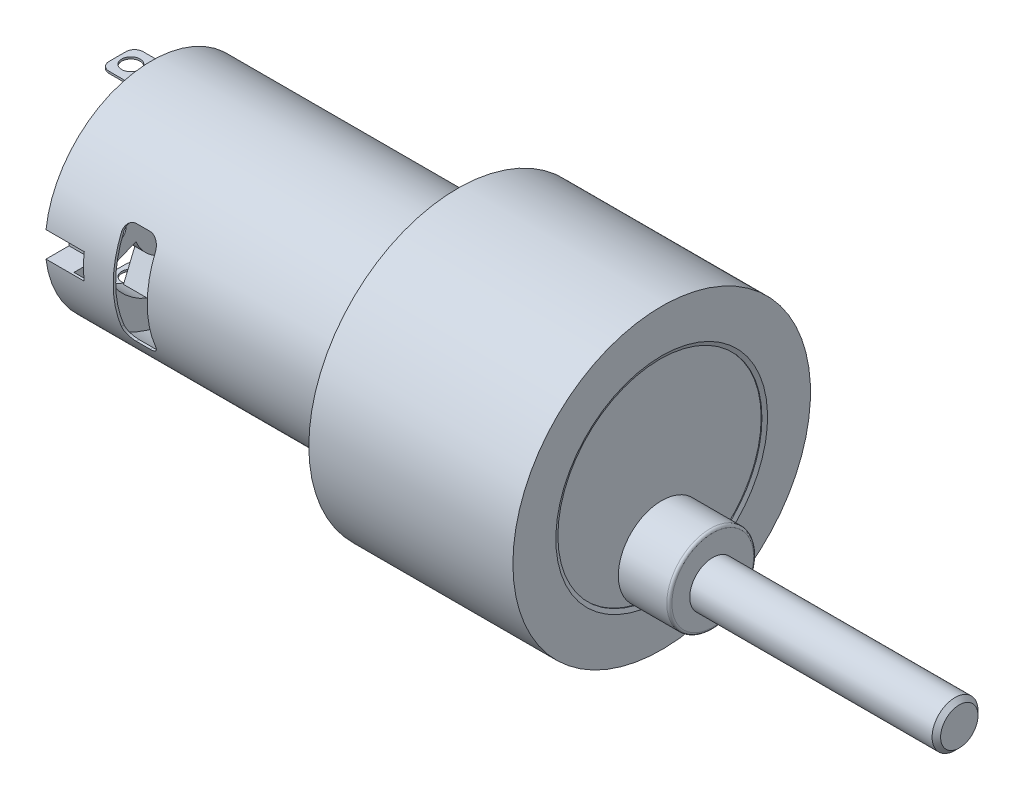
SolidWorks part; units mm, degrees
ref_plane "Front Plane" through (0, 0, 0) normal (0, 0, 1) x (1, 0, 0)
ref_plane "Top Plane" through (0, 0, 0) normal (0, 1, 0) x (1, 0, 0)
ref_plane "Right Plane" through (0, 0, 0) normal (1, 0, 0) x (0, 0, -1)
sketch "Sketch2" plane through (0, 0, 0) normal (0, 0, 1) x (1, 0, 0)
  line L0 (0, -48.3209) -> (0, 42.2888) construction
  line L1 (-76.6203, 0) -> (78.8021, 0) construction
  line L3 (0, -12.5) -> (-36, -12.5)
  line L4 (0, -12.5) -> (0, 0)
  line L5 (0, 0) -> (-36, 0)
  line L6 (-36, -12.5) -> (-36, 0)
  dimension "D1" = 0
  dimension "D2" = 12.5
  dimension "D3" = 36
revolve "Revolve3" add sketch "Sketch2" angle 360 about L1
sketch "Sketch3" plane through (0, 0, 0) normal (0, 0, 1) x (1, 0, 0)
  line L0 (-70.2271, 0) -> (43.535, 0) construction
  line L2 (0, 0) -> (24, 0)
  line L3 (0, 0) -> (0, -17.5)
  line L4 (0, -17.5) -> (24, -17.5)
  line L5 (24, 0) -> (24, -17.5)
  dimension "D1" = 17.5
  dimension "D2" = 24
revolve "Revolve4" add sketch "Sketch3" angle 360 about L0
sketch "Sketch4" plane through (0, 0, 0) normal (0, 0, 1) x (1, 0, 0)
  line L0 (47.6634, 0) -> (-40.4502, 0) construction
  line L2 (24, 17.5) -> (0, 17.5) construction
  line L3 (24, -7.4) -> (30, -7.4)
  line L4 (24, -7.4) -> (24, -12.5)
  line L5 (24, -12.5) -> (30, -12.5)
  line L6 (30, -7.4) -> (30, -12.5)
  line L7 (0, -17.5) -> (24, -17.5) construction
  line L8 (24, -17.5) -> (24, 17.5) construction
  dimension "D1" = 24.9
  dimension "D2" = 5
  dimension "D3" = 0
  dimension "D4" = 6
revolve "Revolve6" add sketch "Sketch4" angle 360 about L3
sketch "Sketch5" plane through (0, 0, 0) normal (0, 0, 1) x (1, 0, 0)
  line L0 (30, -12.5) -> (30, -2.3) construction
  line L1 (30, -7.8) -> (59, -7.8)
  line L2 (30, -7.8) -> (30, -10.5)
  line L3 (30, -10.5) -> (59, -10.5)
  line L4 (59, -7.8) -> (59, -10.5)
  line L5 (30, -2.3) -> (24, -2.3) construction
  line L6 (24, -12.5) -> (30, -12.5) construction
  dimension "D1" = 0
  dimension "D2" = 5.5
  dimension "D3" = 2
  dimension "D4" = 29
revolve "Revolve7" add sketch "Sketch5" angle 360 about L1
sketch "Sketch6" plane through (-36, 0, 0) normal (-1, 0, 0) x (0, 0, 1)
  line L0 (-25.7397, 0) -> (23.7541, 0) construction
  line L1 (9.7, -1.5) -> (9.7, 1.5)
  line L2 (-12.7, 1.5) -> (-9.7, 1.5)
  line L3 (-12.7, 1.5) -> (-12.7, -1.5)
  line L4 (-12.7, -1.5) -> (-9.7, -1.5)
  line L5 (-9.7, 1.5) -> (-9.7, -1.5)
  line L6 (12.7, 1.5) -> (9.7, 1.5)
  line L7 (12.7, -1.5) -> (12.7, 1.5)
  line L8 (12.7, -1.5) -> (9.7, -1.5)
  circle A0 centre (0, 0) radius 12.5 construction
  point P16 (0, 0)
  dimension "D1" = 1.5
  dimension "D2" = 1.5
  dimension "D3" = 12.7
  dimension "D4" = 3
  dimension "D5" = 2
extrude "Cut-Extrude1" cut sketch "Sketch6" against normal blind 4.5
sketch "Sketch7" plane through (-36, 0, 0) normal (-1, 0, 0) x (0, 0, 1)
  line L0 (-29.5362, 0) -> (27.1489, 0) construction
  line L1 (0, -19.8347) -> (0, 19.3268) construction
  circle A0 centre (0, 0) radius 5
extrude "Boss-Extrude1" add sketch "Sketch7" along normal blind 2
sketch "Sketch8" plane through (-38, 0, 0) normal (-1, 0, 0) x (0, 0, 1)
  line L0 (0, 21.7277) -> (0, -11.2834) construction
  line L1 (-20.7897, 0) -> (18.4052, 0) construction
  circle A0 centre (0, 0) radius 1
extrude "Boss-Extrude2" add sketch "Sketch8" along normal blind 1.25
fillet "Fillet1" radius 0.3 1 edges at (-39.25, 0, 1)
sketch "Sketch9" plane through (-38, 0, 0) normal (-1, 0, 0) x (0, 0, 1)
  line L0 (-9.217, 0) -> (10.8718, 0) construction
  line L1 (0, 7.5953) -> (0, -8.4183) construction
  circle A0 centre (0, 0) radius 2
extrude "Cut-Extrude3" cut sketch "Sketch9" against normal blind 0.1
sketch "Sketch10" plane through (-36, 0, 0) normal (-1, 0, 0) x (0, 0, 1)
  line L0 (0, 16.1566) -> (0, -22.5452) construction
  line L1 (-18.3449, 0) -> (20.5959, 0) construction
  circle A0 centre (0, 0) radius 9.1289
extrude "Cut-Extrude6" cut sketch "Sketch10" against normal blind 0.2
sketch "Sketch11" plane through (-35.8, 0, 0) normal (-1, 0, 0) x (0, 0, 1)
  line L0 (0, 19.2252) -> (0, -19.1236) construction
  line L1 (-30.9584, 0) -> (29.1806, 0) construction
  line L2 (3.4935, 8.434) -> (0, 0) construction
  line L3 (0, 0) -> (8.434, 3.4935) construction
  line L4 (2.001, 4.8309) -> (3.4935, 8.434)
  line L5 (4.8309, 2.001) -> (8.434, 3.4935)
  line L6 (4.8309, -2.001) -> (8.434, -3.4935)
  line L7 (2.001, -4.8309) -> (3.4935, -8.434)
  line L8 (-2.001, -4.8309) -> (-3.4935, -8.434)
  line L9 (-4.8309, -2.001) -> (-8.434, -3.4935)
  line L10 (-4.8309, 2.001) -> (-8.434, 3.4935)
  line L11 (-2.001, 4.8309) -> (-3.4935, 8.434)
  arc A0 (8.434, 3.4935) -> (3.4935, 8.434) centre (0, 0) ccw
  circle A1 centre (0, 0) radius 9.1289 construction
  arc A2 (4.8309, 2.001) -> (2.001, 4.8309) centre (0, 0) ccw
  arc A3 (3.4935, -8.434) -> (8.434, -3.4935) centre (0, 0) ccw
  arc A4 (2.001, -4.8309) -> (4.8309, -2.001) centre (0, 0) ccw
  arc A5 (-8.434, -3.4935) -> (-3.4935, -8.434) centre (0, 0) ccw
  arc A6 (-4.8309, -2.001) -> (-2.001, -4.8309) centre (0, 0) ccw
  arc A7 (-3.4935, 8.434) -> (-8.434, 3.4935) centre (0, 0) ccw
  arc A8 (-2.001, 4.8309) -> (-4.8309, 2.001) centre (0, 0) ccw
  circle A9 centre (7, 0) radius 1
  circle A10 centre (-7, 0) radius 1
  point P28 (0, 0)
  dimension "D2" = 3.9
  dimension "D5" = 7
  dimension "D7" = 2
  dimension "D8" = 2
  dimension "D1" = 45
  dimension "D3" = 22.5
  dimension "D6" = 7
  dimension "D4" = 4
extrude "Cut-Extrude7" cut sketch "Sketch11" against normal blind 3
sketch "Sketch12" plane through (0, 0, 0) normal (0, 1, 0) x (1, 0, 0)
  line L0 (-50.7107, 0) -> (53.9056, 0) construction
  line L2 (-33, 0) -> (-2, 0)
  line L3 (-33, 0) -> (-33, -12.2097)
  line L4 (-33, -12.2097) -> (-2, -12.2097)
  line L5 (-2, 0) -> (-2, -12.2097)
  line L6 (-31.5, -12.4097) -> (-36, -12.4097) construction
  line L7 (0, 12.5) -> (0, -12.5) construction
  line L8 (-36, 12.4097) -> (-36, -12.4097) construction
  dimension "D1" = 0
  dimension "D2" = 0.2
  dimension "D3" = 2
  dimension "D4" = 3
revolve "Cut-Revolve2" cut sketch "Sketch12" angle 360 about L0
fillet "Fillet2" radius 0.3 1 edges at (30, -7.4, 5.1)
chamfer "Chamfer1" distance 0.5 angle 45 1 edges at (59, -7.8, 2.7)
sketch "Sketch13" plane through (-36, 0, 0) normal (-1, 0, 0) x (0, 0, 1)
  line L0 (0, 12.5) -> (0, -7.0928) construction
  line L1 (-15.8773, 12.5) -> (14.8647, 12.5) construction
  line L2 (-2, 10.7) -> (2, 10.7)
  line L3 (-2, 10.7) -> (-2, 10.9289)
  line L4 (-2, 10.9289) -> (2, 10.9289)
  line L5 (2, 10.7) -> (2, 10.9289)
  line L6 (20.0804, 9.1289) -> (-14.9303, 9.1289) construction
  arc A2 (12.4097, 1.5) -> (-12.4097, 1.5) centre (0, 0) ccw construction
  circle A3 centre (0, 0) radius 17.5 construction
  circle A4 centre (0, 0) radius 9.1289 construction
  dimension "D1" = 1.8
  dimension "D2" = 1.8
  dimension "D3" = 2
  dimension "D4" = 2
extrude "Boss-Extrude4" add sketch "Sketch13" along normal blind 4
sketch "Sketch14" plane through (0, 10.9289, 0) normal (0, 1, 0) x (1, 0, 0)
  line L0 (-40, -2) -> (-40, 2) construction
  circle A0 centre (-38.4225, 0) radius 1.0775
  dimension "D1" = 1.5775
extrude "Cut-Extrude8" cut sketch "Sketch14" against normal up to surface (0.2289 mm away) up to face at (-38, 10.7, 0)
fillet "Fillet3" radius 1 1 edges at (-40, 10.8145, -2)
fillet "Fillet5" radius 1 1 edges at (-40, 10.8145, 2)
mirror "Mirror3" about plane through (0, 0, 0) normal (0, 1, 0) of "Boss-Extrude4", "Cut-Extrude8", "Fillet3", "Fillet5"
sketch "Sketch15" plane through (0, 0, 0) normal (0, 0, 1) x (1, 0, 0)
  line L0 (-44.9549, 0) -> (63.0668, 0) construction
  line L1 (-28, 4.8) -> (-28, -4.8)
  line L2 (-26.8, -6) -> (-25.2, -6)
  line L3 (-24, -4.8) -> (-24, 4.8)
  line L4 (-25.2, 6) -> (-26.8, 6)
  line L5 (-36, 12.5) -> (-36, 1.5) construction
  arc A0 (-26.8, 6) -> (-28, 4.8) centre (-26.8, 4.8) ccw
  arc A1 (-28, -4.8) -> (-26.8, -6) centre (-26.8, -4.8) ccw
  arc A2 (-25.2, -6) -> (-24, -4.8) centre (-25.2, -4.8) ccw
  arc A3 (-24, 4.8) -> (-25.2, 6) centre (-25.2, 4.8) ccw
  point P11 (-28, 6)
  point P14 (-28, -6)
  point P17 (-24, -6)
  dimension "D4" = 1.2
  dimension "D5" = 1.2
  dimension "D1" = 12
  dimension "D2" = 4
  dimension "D3" = 8
extrude "Cut-Extrude9" cut sketch "Sketch15" against normal through all both and the other way through all
sketch "Sketch16" plane through (0, 0, 0) normal (0, 1, 0) x (1, 0, 0)
  line L0 (-43.8447, 0) -> (18.326, 0) construction
sketch "Sketch17" plane through (24, 0, 0) normal (1, 0, 0) x (0, 0, -1)
  line L0 (0, 27.0341) -> (0, -26.1463) construction
  line L1 (-41.2114, 0) -> (40.4143, 0) construction
  circle A0 centre (0, 0) radius 12
extrude "Cut-Extrude10" cut sketch "Sketch17" against normal blind 0.3 contours A0
chamfer "Chamfer2" distance 0.45 angle 25 1 edges at (24, 12, 0) first distance on face at (24, -0.25, 0)
